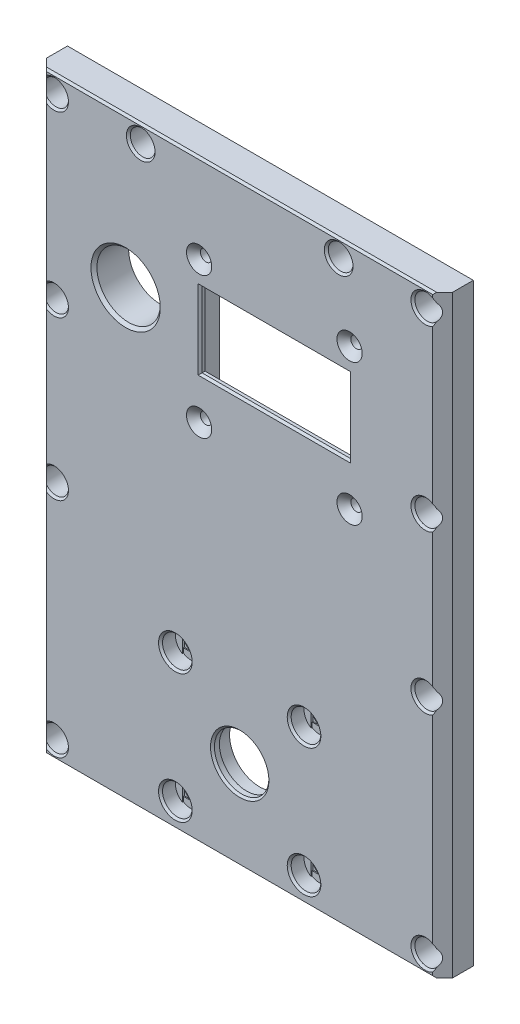
SolidWorks part; units mm, degrees
ref_plane "Front Plane" through (0, 0, 0) normal (0, 0, 1) x (1, 0, 0)
ref_plane "Top Plane" through (0, 0, 0) normal (0, 1, 0) x (1, 0, 0)
ref_plane "Right Plane" through (0, 0, 0) normal (1, 0, 0) x (0, 0, -1)
sketch "Sketch1" plane through (0, 0, 0) normal (0, 0, 1) x (1, 0, 0)
  line L1 (-41, -60) -> (41, -60)
  line L2 (-41, -60) -> (-41, 60)
  line L3 (-41, 60) -> (41, 60)
  line L4 (41, -60) -> (41, 60)
  line L5 (-41, -60) -> (41, 60) construction
  line L6 (-41, 60) -> (41, -60) construction
  line L7 (-34, -53) -> (34, -53)
  line L8 (-34, -53) -> (-34, 53)
  line L9 (-34, 53) -> (34, 53)
  line L10 (34, -53) -> (34, 53)
  line L11 (-34, -53) -> (34, 53) construction
  line L12 (-34, 53) -> (34, -53) construction
  point P0 (0, 0)
  point P6 (0, 0)
  dimension "D1" = 120
  dimension "D2" = 82
  dimension "D3" = 7
  dimension "D4" = 7
extrude "Boss-Extrude1" add sketch "Sketch1" along normal blind 7
sketch "Sketch2" plane through (0, 0, 7) normal (0, 0, 1) x (1, 0, 0)
  line L0 (34, -53) -> (34, 53) construction
  line L1 (-34, -53) -> (34, -53)
  line L2 (-34, -53) -> (-34, -17)
  line L3 (-34, -17) -> (34, -17)
  line L4 (34, -53) -> (34, -17)
  dimension "D1" = 36
extrude "Boss-Extrude2" add sketch "Sketch2" against normal up to surface (7 mm away) up to face at (0, 0, 0)
sketch "Sketch3" plane through (0, 0, 0) normal (0, 0, -1) x (-1, 0, 0)
  line L0 (0, -60) -> (0, -42) construction
  line L1 (41, -60) -> (-41, -60) construction
  circle A0 centre (0, -42) radius 5.5
  dimension "D1" = 11
  dimension "D2" = 18
extrude "Cut-Extrude1" cut sketch "Sketch3" against normal through all
sketch "Sketch4" plane through (0, 0, 0) normal (0, 0, -1) x (-1, 0, 0)
  circle A0 centre (0, -42) radius 6.05
  dimension "D1" = 12.1
extrude "Cut-Extrude2" cut sketch "Sketch4" against normal offset from surface (5.6 mm away) 1.4 up to face at (-5.5, -42, 7)
sketch "Sketch5" plane through (0, 0, 0) normal (0, 0, -1) x (-1, 0, 0)
  circle A0 centre (0, -42) radius 11.1
  dimension "D1" = 22.2
extrude "Cut-Extrude3" cut sketch "Sketch5" against normal offset from surface (3 mm away) 2.6 up to face at (-6.05, -42, 5.6)
sketch "Sketch6" plane through (0, 0, 0) normal (0, 0, -1) x (-1, 0, 0)
  line L1 (-13, -55) -> (13, -55) construction
  line L2 (-13, -55) -> (-13, -29) construction
  line L3 (-13, -29) -> (13, -29) construction
  line L4 (13, -55) -> (13, -29) construction
  line L5 (-13, -55) -> (13, -29) construction
  line L6 (-13, -29) -> (13, -55) construction
  circle A0 centre (-13, -29) radius 1.6
  circle A1 centre (13, -29) radius 1.6
  circle A2 centre (13, -55) radius 1.6
  circle A3 centre (-13, -55) radius 1.6
  point P0 (0, -42)
  dimension "D2" = 3.2
  dimension "D1" = 26
extrude "Cut-Extrude4" cut sketch "Sketch6" against normal through all
sketch "Sketch7" plane through (0, 0, 0) normal (0, 0, -1) x (-1, 0, 0)
  line L1 (-25, -61) -> (25, -61)
  line L2 (-25, -61) -> (-25, -23)
  line L3 (-25, -23) -> (25, -23)
  line L4 (25, -61) -> (25, -23)
  line L5 (-25, -61) -> (25, -23) construction
  line L6 (-25, -23) -> (25, -61) construction
  point P0 (0, -42)
  dimension "D1" = 50
  dimension "D2" = 38
extrude "Cut-Extrude5" cut sketch "Sketch7" against normal blind 1
sketch "Sketch8" plane through (0, 0, 7) normal (0, 0, 1) x (1, 0, 0)
  circle A0 centre (-13, -29) radius 3
  circle A1 centre (13, -29) radius 3
  circle A2 centre (13, -55) radius 3
  circle A3 centre (-13, -55) radius 3
  dimension "D1" = 6
extrude "Cut-Extrude6" cut sketch "Sketch8" against normal blind 3
sketch "Sketch9" plane through (0, 0, 7) normal (0, 0, 1) x (1, 0, 0)
  line L0 (-41, 60) -> (-41, -60) construction
  line L1 (-37.5, -56.5) -> (37.5, -56.5) construction
  line L2 (-37.5, -56.5) -> (-37.5, 56.5) construction
  line L3 (-37.5, 56.5) -> (37.5, 56.5) construction
  line L4 (37.5, -56.5) -> (37.5, 56.5) construction
  line L5 (-37.5, -56.5) -> (37.5, 56.5) construction
  line L6 (-37.5, 56.5) -> (37.5, -56.5) construction
  line L7 (41, 60) -> (-41, 60) construction
  circle A0 centre (-37.5, 56.5) radius 1.5
  circle A1 centre (37.5, 56.5) radius 1.5
  circle A2 centre (37.5, -56.5) radius 1.5
  circle A3 centre (-37.5, -56.5) radius 1.5
  circle A6 centre (-37.5, 20.5) radius 1.5
  circle A7 centre (-37.5, -11.5) radius 1.5
  circle A8 centre (37.5, -11.5) radius 1.5
  circle A9 centre (37.5, 20.5) radius 1.5
  point P0 (0, 0)
  dimension "D3" = 3
  dimension "D4" = 45
  dimension "D5" = 36
  dimension "D1" = 3.5
  dimension "D2" = 3.5
extrude "Cut-Extrude7" cut sketch "Sketch9" against normal through all
sketch "Sketch10" plane through (0, 0, 7) normal (0, 0, 1) x (1, 0, 0)
  circle A0 centre (-37.5, 56.5) radius 2.5
  circle A1 centre (37.5, 56.5) radius 2.5
  circle A2 centre (-37.5, 20.5) radius 2.5
  circle A3 centre (-37.5, -11.5) radius 2.5
  circle A4 centre (-37.5, -56.5) radius 2.5
  circle A5 centre (37.5, -56.5) radius 2.5
  circle A6 centre (37.5, 20.5) radius 2.5
  circle A7 centre (37.5, -11.5) radius 2.5
  dimension "D1" = 5
extrude "Cut-Extrude8" cut sketch "Sketch10" against normal blind 5
chamfer "Chamfer1" distance 2 angle 45 2 edges at (-41, 0, 7) (41, 0, 7)
sketch "Sketch11" plane through (0, 0, 7) normal (0, 0, 1) x (1, 0, 0)
  line L0 (34, -17) -> (34, 53) construction
  line L1 (-34, -17) -> (34, -17)
  line L2 (-34, -17) -> (-34, 2)
  line L3 (-34, 2) -> (34, 2)
  line L4 (34, -17) -> (34, 2)
  line L5 (-39, -60) -> (39, -60) construction
  dimension "D1" = 62
extrude "Boss-Extrude3" add sketch "Sketch11" against normal up to surface (7 mm away) up to face at (39, 56.5, 0)
sketch "Sketch12" plane through (0, 0, 2) normal (0, 0, 1) x (1, 0, 0)
  line L2 (-39, -58.5) -> (-39, -54.5)
  line L4 (-36, -58.5) -> (-36, -54.5)
  line L5 (-39, -58.5) -> (-36, -54.5) construction
  line L6 (-39, -54.5) -> (-36, -58.5) construction
  line L8 (-39, -13.5) -> (-39, -9.5)
  line L10 (-36, -13.5) -> (-36, -9.5)
  line L11 (-39, -13.5) -> (-36, -9.5) construction
  line L12 (-39, -9.5) -> (-36, -13.5) construction
  line L14 (-39, 18.5) -> (-39, 22.5)
  line L16 (-36, 18.5) -> (-36, 22.5)
  line L17 (-39, 18.5) -> (-36, 22.5) construction
  line L18 (-39, 22.5) -> (-36, 18.5) construction
  line L20 (-39, 54.5) -> (-39, 58.5)
  line L22 (-36, 54.5) -> (-36, 58.5)
  line L23 (-39, 54.5) -> (-36, 58.5) construction
  line L24 (-39, 58.5) -> (-36, 54.5) construction
  arc A0 (-39, -58.5) -> (-39, -54.5) centre (-37.5, -56.5) ccw construction
  circle A1 centre (-37.5, -11.5) radius 2.5 construction
  circle A2 centre (-37.5, 20.5) radius 2.5 construction
  arc A3 (-39, 54.5) -> (-39, 58.5) centre (-37.5, 56.5) ccw construction
  circle A4 centre (-37.5, 56.5) radius 1.5 construction
  circle A5 centre (-37.5, 56.5) radius 2.5 construction
  arc A6 (-36, 58.5) -> (-39, 58.5) centre (-37.5, 56.5) ccw
  arc A7 (-39, 54.5) -> (-36, 54.5) centre (-37.5, 56.5) ccw
  circle A8 centre (-37.5, 20.5) radius 1.5 construction
  arc A9 (-39, 18.5) -> (-36, 18.5) centre (-37.5, 20.5) ccw
  arc A10 (-36, 22.5) -> (-39, 22.5) centre (-37.5, 20.5) ccw
  circle A11 centre (-37.5, -11.5) radius 1.5 construction
  arc A12 (-39, -13.5) -> (-36, -13.5) centre (-37.5, -11.5) ccw
  arc A13 (-36, -9.5) -> (-39, -9.5) centre (-37.5, -11.5) ccw
  circle A14 centre (-37.5, -56.5) radius 1.5 construction
  arc A16 (-39, -58.5) -> (-36, -58.5) centre (-37.5, -56.5) ccw
  arc A18 (-36, -54.5) -> (-39, -54.5) centre (-37.5, -56.5) ccw
  point P0 (-37.5, -56.5)
  point P9 (-37.5, -11.5)
  point P17 (-37.5, 20.5)
  point P25 (-37.5, 56.5)
extrude "Cut-Extrude9" cut sketch "Sketch12" against normal blind 0.2
sketch "Sketch13" plane through (0, 0, 1.8) normal (0, 0, 1) x (1, 0, 0)
  line L0 (-36, -56.5) -> (-36, -54.5) construction
  line L1 (-39, -58) -> (-36, -58)
  line L2 (-39, -58) -> (-39, -55)
  line L3 (-39, -55) -> (-36, -55)
  line L4 (-36, -58) -> (-36, -55)
  line L5 (-39, -58) -> (-36, -55) construction
  line L6 (-39, -55) -> (-36, -58) construction
  line L7 (-36, -11.5) -> (-36, -9.5) construction
  line L8 (-39, -13) -> (-36, -13)
  line L9 (-39, -13) -> (-39, -10)
  line L10 (-39, -10) -> (-36, -10)
  line L11 (-36, -13) -> (-36, -10)
  line L12 (-39, -13) -> (-36, -10) construction
  line L13 (-39, -10) -> (-36, -13) construction
  line L14 (-36, 18.5) -> (-36, 22.5) construction
  line L15 (-39, 19) -> (-36, 19)
  line L16 (-39, 19) -> (-39, 22)
  line L17 (-39, 22) -> (-36, 22)
  line L18 (-36, 19) -> (-36, 22)
  line L19 (-39, 19) -> (-36, 22) construction
  line L20 (-39, 22) -> (-36, 19) construction
  line L21 (-36, 54.5) -> (-36, 58.5) construction
  line L22 (-39, 55) -> (-36, 55)
  line L23 (-39, 55) -> (-39, 58)
  line L24 (-39, 58) -> (-36, 58)
  line L25 (-36, 55) -> (-36, 58)
  line L26 (-39, 55) -> (-36, 58) construction
  line L27 (-39, 58) -> (-36, 55) construction
  arc A0 (-36, -56.5) -> (-39, -56.5) centre (-37.5, -56.5) ccw construction
  arc A1 (-36, -11.5) -> (-39, -11.5) centre (-37.5, -11.5) ccw construction
  arc A2 (-36, 20.5) -> (-39, 20.5) centre (-37.5, 20.5) ccw construction
  arc A3 (-36, 56.5) -> (-39, 56.5) centre (-37.5, 56.5) ccw construction
  point P0 (-37.5, -56.5)
  point P11 (-37.5, -11.5)
  point P22 (-37.5, 20.5)
  point P33 (-37.5, 56.5)
extrude "Cut-Extrude10" cut sketch "Sketch13" against normal blind 0.2
sketch "Sketch14" plane through (0, 0, 4) normal (0, 0, 1) x (1, 0, 0)
  line L2 (-14.6, -31.5377) -> (-14.6, -26.4623)
  line L4 (-11.4, -31.5377) -> (-11.4, -26.4623)
  line L5 (-14.6, -31.5377) -> (-11.4, -26.4623) construction
  line L6 (-14.6, -26.4623) -> (-11.4, -31.5377) construction
  line L8 (-14.6, -57.5377) -> (-14.6, -52.4623)
  line L10 (-11.4, -57.5377) -> (-11.4, -52.4623)
  line L11 (-14.6, -57.5377) -> (-11.4, -52.4623) construction
  line L12 (-14.6, -52.4623) -> (-11.4, -57.5377) construction
  circle A0 centre (-13, -29) radius 3 construction
  circle A1 centre (-13, -55) radius 3 construction
  circle A2 centre (-13, -29) radius 3 construction
  arc A3 (-14.6, -31.5377) -> (-11.4, -31.5377) centre (-13, -29) ccw
  arc A4 (-14.6, -57.5377) -> (-11.4, -57.5377) centre (-13, -55) ccw
  circle A5 centre (-13, -29) radius 1.6 construction
  circle A6 centre (-13, -55) radius 1.6 construction
  arc A7 (-11.4, -26.4623) -> (-14.6, -26.4623) centre (-13, -29) ccw
  arc A8 (-11.4, -52.4623) -> (-14.6, -52.4623) centre (-13, -55) ccw
  point P0 (-13, -29)
  point P8 (-13, -55)
extrude "Cut-Extrude11" cut sketch "Sketch14" against normal blind 0.2
sketch "Sketch15" plane through (0, 0, 3.8) normal (0, 0, 1) x (1, 0, 0)
  line L0 (-11.4, -29) -> (-11.4, -26.4623) construction
  line L1 (-14.6, -30.6) -> (-11.4, -30.6)
  line L2 (-14.6, -30.6) -> (-14.6, -27.4)
  line L3 (-14.6, -27.4) -> (-11.4, -27.4)
  line L4 (-11.4, -30.6) -> (-11.4, -27.4)
  line L5 (-14.6, -30.6) -> (-11.4, -27.4) construction
  line L6 (-14.6, -27.4) -> (-11.4, -30.6) construction
  line L7 (-11.4, -55) -> (-11.4, -52.4623) construction
  line L8 (-14.6, -56.6) -> (-11.4, -56.6)
  line L9 (-14.6, -56.6) -> (-14.6, -53.4)
  line L10 (-14.6, -53.4) -> (-11.4, -53.4)
  line L11 (-11.4, -56.6) -> (-11.4, -53.4)
  line L12 (-14.6, -56.6) -> (-11.4, -53.4) construction
  line L13 (-14.6, -53.4) -> (-11.4, -56.6) construction
  arc A0 (-11.4, -55) -> (-14.6, -55) centre (-13, -55) ccw construction
  arc A1 (-14.6, -29) -> (-11.4, -29) centre (-13, -29) ccw construction
  point P0 (-13, -29)
  point P8 (-13, -55)
extrude "Cut-Extrude12" cut sketch "Sketch15" against normal blind 0.2
mirror "Mirror1" about plane through (0, 0, 0) normal (1, 0, 0) of "Cut-Extrude10", "Cut-Extrude11", "Cut-Extrude12", "Cut-Extrude9"
chamfer "Chamfer2" distance 0.4 angle 45 4 edges at (34, 27.5, 7) (0, 53, 7) (0, 2, 7) (-34, 27.5, 7)
chamfer "Chamfer3" distance 0.8 angle 45 2 edges at (-41, 0, 0) (41, 0, 0)
sketch "Sketch16" plane through (0, 0, 0) normal (1, 0, 0) x (0, 0, -1)
  line L0 (0, -4) -> (0, -15.4)
  line L1 (0, 60) -> (0, -60) construction
  line L2 (0, -15.4) -> (3.2, -12.2)
  line L3 (3.2, -12.2) -> (3.2, -7.2)
  line L4 (3.2, -7.2) -> (0, -4)
  line L5 (0, -15.4) -> (0, -19.4) construction
  line L6 (0.6, -7.7) -> (2.6, -7.7)
  line L7 (0.6, -7.7) -> (0.6, -11.7)
  line L8 (0.6, -11.7) -> (2.6, -11.7)
  line L9 (2.6, -7.7) -> (2.6, -11.7)
  line L10 (-1.046, -17.4) -> (12.8392, -17.4) construction
  line L11 (2.6, -27.1) -> (2.6, -23.1)
  line L12 (0.6, -23.1) -> (2.6, -23.1)
  line L13 (0.6, -27.1) -> (0.6, -23.1)
  line L14 (0.6, -27.1) -> (2.6, -27.1)
  line L15 (3.2, -27.6) -> (0, -30.8)
  line L16 (3.2, -22.6) -> (3.2, -27.6)
  line L17 (0, -19.4) -> (3.2, -22.6)
  line L18 (0, -30.8) -> (0, -19.4)
  point P10 (2.6, -9.7)
  point P11 (3.2, -9.7)
  point P24 (0, -17.4)
  dimension "D1" = 5
  dimension "D2" = 2
  dimension "D3" = 0.6
  dimension "D4" = 0.6
  dimension "D5" = 45
  dimension "D6" = 4
  dimension "D7" = 4
  dimension "D8" = 4
extrude "Boss-Extrude4" add sketch "Sketch16" along normal mid plane 2
pattern_linear "LPattern1" count 2 spacing 20 along (1, 0, 0) count 2 spacing 20 along (-1, 0, 0) of "Boss-Extrude4"
sketch "Sketch17" plane through (0, 0, 0) normal (0, 0, -1) x (-1, 0, 0)
  line L0 (-20, 56.5) -> (20, 56.5) construction
  line L1 (-40.2, 60) -> (40.2, 60) construction
  circle A0 centre (-37.5, 56.5) radius 1.5 construction
  circle A1 centre (-37.5, 56.5) radius 1.5 construction
  circle A2 centre (-20, 56.5) radius 1.5
  circle A3 centre (20, 56.5) radius 1.5
  point P3 (0, 56.5)
  point P6 (0, 60)
  dimension "D1" = 40
extrude "Cut-Extrude13" cut sketch "Sketch17" against normal through all
sketch "Sketch18" plane through (0, 0, 7) normal (0, 0, 1) x (1, 0, 0)
  circle A0 centre (-20, 56.5) radius 2.5
  circle A1 centre (20, 56.5) radius 2.5
  arc A2 (-39, 54.5) -> (-39, 58.5) centre (-37.5, 56.5) ccw construction
extrude "Cut-Extrude14" cut sketch "Sketch18" against normal up to surface (5 mm away) up to face at (35.5, 56.5, 2)
sketch "Sketch19" plane through (0, 0, 2) normal (0, 0, 1) x (1, 0, 0)
  line L2 (-21.5, 54.5) -> (-21.5, 58.5)
  line L4 (-18.5, 54.5) -> (-18.5, 58.5)
  line L5 (-21.5, 54.5) -> (-18.5, 58.5) construction
  line L6 (-21.5, 58.5) -> (-18.5, 54.5) construction
  line L8 (18.5, 54.5) -> (18.5, 58.5)
  line L10 (21.5, 54.5) -> (21.5, 58.5)
  line L11 (18.5, 54.5) -> (21.5, 58.5) construction
  line L12 (18.5, 58.5) -> (21.5, 54.5) construction
  circle A0 centre (-20, 56.5) radius 2.5 construction
  circle A1 centre (20, 56.5) radius 2.5 construction
  circle A2 centre (20, 56.5) radius 1.5 construction
  circle A3 centre (-20, 56.5) radius 1.5 construction
  circle A4 centre (-20, 56.5) radius 2.5 construction
  arc A5 (18.5, 54.5) -> (21.5, 54.5) centre (20, 56.5) ccw
  arc A6 (-18.5, 58.5) -> (-21.5, 58.5) centre (-20, 56.5) ccw
  arc A7 (21.5, 58.5) -> (18.5, 58.5) centre (20, 56.5) ccw
  arc A8 (-21.5, 54.5) -> (-18.5, 54.5) centre (-20, 56.5) ccw
  point P0 (-20, 56.5)
  point P8 (20, 56.5)
extrude "Cut-Extrude15" cut sketch "Sketch19" against normal blind 0.2
sketch "Sketch20" plane through (0, 0, 1.8) normal (0, 0, 1) x (1, 0, 0)
  line L0 (-18.5, 54.5) -> (-18.5, 58.5) construction
  line L1 (-21.5, 55) -> (-18.5, 55)
  line L2 (-21.5, 55) -> (-21.5, 58)
  line L3 (-21.5, 58) -> (-18.5, 58)
  line L4 (-18.5, 55) -> (-18.5, 58)
  line L5 (-21.5, 55) -> (-18.5, 58) construction
  line L6 (-21.5, 58) -> (-18.5, 55) construction
  line L7 (21.5, 56.5) -> (21.5, 58.5) construction
  line L8 (18.5, 55) -> (21.5, 55)
  line L9 (18.5, 55) -> (18.5, 58)
  line L10 (18.5, 58) -> (21.5, 58)
  line L11 (21.5, 55) -> (21.5, 58)
  line L12 (18.5, 55) -> (21.5, 58) construction
  line L13 (18.5, 58) -> (21.5, 55) construction
  arc A0 (18.5, 56.5) -> (21.5, 56.5) centre (20, 56.5) ccw construction
  point P0 (-20, 56.5)
  point P8 (20, 56.5)
extrude "Cut-Extrude16" cut sketch "Sketch20" against normal blind 0.2
sketch "Skizze4" plane through (0, 0, 0) normal (0, 0, -1) x (-1, 0, 0)
  line L1 (21, -4) -> (-21, -4)
  line L2 (21, -4) -> (21, -30.8)
  line L3 (21, -30.8) -> (-21, -30.8)
  line L4 (-21, -4) -> (-21, -30.8)
extrude "Schnitt-Linear austragen1" cut sketch "Skizze4" along normal up to surface (3.2 mm away) up to face at (-20, -9.7, -3.2)
sketch "Skizze6" plane through (0, 0, 7) normal (0, 0, 1) x (1, 0, 0)
  line L0 (12.4, 53.4) -> (34.4, 31.4) construction
  line L1 (34.4, 53.4) -> (12.4, 53.4)
  line L2 (34.4, 53.4) -> (34.4, 31.4)
  line L3 (34.4, 31.4) -> (12.4, 31.4)
  line L4 (12.4, 53.4) -> (12.4, 31.4)
  line L5 (23.4, 53.4) -> (23.4, 31.4) construction
  circle A0 centre (23.4, 41.4) radius 8.25
  point P10 (23.4, 42.4)
  dimension "D1" = 16.5
  dimension "D2" = 22
  dimension "D3" = 22
  dimension "D4" = 1
extrude "Aufsatz-Linear austragen1" add sketch "Skizze6" against normal up to surface (7 mm away) up to face at (0, -20.75, 0)
sketch "Skizze7" plane through (0, 0, 7) normal (0, 0, 1) x (1, 0, 0)
  circle A0 centre (23.4, 41.4) radius 9.25
  dimension "D1" = 18.5
extrude "Schnitt-Linear austragen2" cut sketch "Skizze7" against normal blind 1.6
chamfer "Fase6" distance 0.5 angle 45 2 edges at (12.4, 42.4, 7) (23.4, 31.4, 7)
chamfer "Fase7" distance 4 angle 45 1 edges at (12.4, 31.4, 3.25)
chamfer "Fase8" distance 1 angle 45 1 edges at (31.65, 41.4, 5.4)
mirror "Mirror2" about plane through (0, 0, 0) normal (1, 0, 0) of "Fase6", "Schnitt-Linear austragen2", "Fase8", "Aufsatz-Linear austragen1", "Fase7"
sketch "Sketch21" plane through (0, 0, 7) normal (0, 0, 1) x (1, 0, 0)
  line L0 (34.4, 31.9) -> (34.4, 1.6) construction
  line L1 (-34.4, 31.9) -> (-15.9, 31.9)
  line L2 (-34.4, 31.9) -> (-34.4, 15.9)
  line L3 (-34.4, 15.9) -> (34.4, 15.9)
  line L4 (34.4, 31.9) -> (34.4, 15.9)
  line L5 (-15.9, 31.9) -> (-12.4, 35.4)
  line L6 (-12.4, 35.4) -> (-12.4, 31.9)
  line L7 (12.4, 35.4) -> (15.9, 31.9)
  line L8 (12.4, 35.4) -> (12.4, 31.9)
  line L9 (-12.4, 31.9) -> (12.4, 31.9)
  line L10 (15.9, 31.9) -> (34.4, 31.9)
  dimension "D1" = 16
extrude "Boss-Extrude5" add sketch "Sketch21" against normal up to surface (7 mm away) up to face at (0, 30.64, 0)
chamfer "Chamfer4" distance 0.5 angle 45 7 edges at (12.65, 35.15, 7) (12.4, 33.65, 7) (0, 31.9, 7) (-12.4, 33.65, 7) (-12.65, 35.15, 7) (12.4, 35.4, 6.75) (-12.4, 35.4, 6.75)
sketch "Sketch22" plane through (0, 0, 0) normal (0, 0, -1) x (-1, 0, 0)
  line L0 (0, 31.9) -> (0, 15.9) construction
  line L1 (-12.4, 31.9) -> (12.4, 31.9) construction
  line L2 (34, 15.9) -> (-34, 15.9) construction
  line L4 (-18.95, 17.75) -> (18.95, 17.75)
  line L5 (-18.95, 17.75) -> (-18.95, 30.05)
  line L6 (-18.95, 30.05) -> (18.95, 30.05)
  line L7 (18.95, 17.75) -> (18.95, 30.05)
  line L8 (-18.95, 17.75) -> (18.95, 30.05) construction
  line L9 (-18.95, 30.05) -> (18.95, 17.75) construction
  point P6 (0, 23.9)
  dimension "D1" = 37.9
  dimension "D2" = 12.3
extrude "Cut-Extrude17" cut sketch "Sketch22" against normal offset from surface (6.4 mm away) 0.6 up to face at (0, 8.75, 7)
sketch "Sketch23" plane through (0, 0, 6.4) normal (0, 0, -1) x (-1, 0, 0)
  line L0 (-18.95, 30.05) -> (-18.95, 17.75) construction
  line L1 (-12.95, 18.55) -> (12.05, 18.55)
  line L2 (-12.95, 18.55) -> (-12.95, 28.55)
  line L3 (-12.95, 28.55) -> (12.05, 28.55)
  line L4 (12.05, 18.55) -> (12.05, 28.55)
  line L5 (-12.95, 18.55) -> (12.05, 28.55) construction
  line L6 (-12.95, 28.55) -> (12.05, 18.55) construction
  line L7 (-18.95, 30.05) -> (18.95, 30.05) construction
  point P0 (-0.45, 23.55)
  dimension "D1" = 25
  dimension "D2" = 10
  dimension "D3" = 6
  dimension "D4" = 1.5
extrude "Cut-Extrude18" cut sketch "Sketch23" against normal through all
chamfer "Chamfer5" distance 0.4 angle 45 1 edges at (0, 15.9, 7)
sketch "Sketch24" plane through (0, 0, 7) normal (0, 0, 1) x (1, 0, 0)
  line L1 (-12.9, 53.4) -> (12.9, 53.4)
  line L2 (-12.9, 53.4) -> (-12.9, 31.4)
  line L3 (-12.9, 31.4) -> (12.9, 31.4)
  line L4 (12.9, 53.4) -> (12.9, 31.4)
  line L5 (-12.4, 53) -> (12.4, 53)
  line L6 (-12.4, 53) -> (-12.4, 31.9)
  line L7 (-12.4, 31.9) -> (12.4, 31.9)
  line L8 (12.4, 53) -> (12.4, 31.9)
extrude "Boss-Extrude6" add sketch "Sketch24" against normal up to vertex (0.5 mm away) up to point (12.4, 31.9, 6.5)
chamfer "Chamfer7" distance 3 angle 45 4 edges at (12.4, 31.9, 3.5) (12.4, 53, 3.5) (-12.4, 53, 3.5) (-12.4, 31.9, 3.5)
chamfer "Chamfer8" distance 0.5 angle 45 8 edges at (12.4, 42.45, 7) (0, 31.9, 7) (0, 53, 7) (-12.4, 42.45, 7) (10.9, 33.4, 7) (10.9, 51.5, 7) (-10.9, 51.5, 7) (-10.9, 33.4, 7)
chamfer "Chamfer9" distance 0.8 angle 45 6 edges at (-34, 8.95, 0) (0, 15.9, 0) (34, 8.95, 0) (0, 2, 0) (-32.6, -60, 0) (0, 60, 0)
sketch "Sketch28" plane through (0, 0, 7) normal (0, 0, 1) x (1, 0, 0)
  circle A0 centre (23.4, 41.4) radius 10
  dimension "D1" = 20
extrude "Boss-Extrude8" add sketch "Sketch28" against normal up to surface (7 mm away) up to face at (0, 8.95, 0)
sketch "Sketch29" plane through (0, 0, 0) normal (0, 0, -1) x (-1, 0, 0)
  line L0 (-9.4, 53) -> (9.4, 53) construction
  line L1 (34.8, 53) -> (-34.8, 53)
  line L2 (34.8, 53) -> (34.8, 1.2)
  line L3 (34.8, 1.2) -> (-34.8, 1.2)
  line L4 (-34.8, 53) -> (-34.8, 1.2)
  line L5 (34.8, 1.2) -> (-34.8, 1.2) construction
  line L6 (34.8, 16.7) -> (34.8, 1.2) construction
  line L7 (-34.8, 1.2) -> (-34.8, 16.7) construction
extrude "Boss-Extrude9" add sketch "Sketch29" against normal up to surface (7 mm away) up to face at (0, 42.45, 7)
sketch "Sketch30" plane through (0, 0, 7) normal (0, 0, 1) x (1, 0, 0)
  line L0 (9.4, 53) -> (10.1071, 53) construction
  line L1 (10.1071, 53) -> (9.6071, 53.5) construction
  line L2 (-10.1071, 53) -> (-9.4, 53) construction
  line L3 (-9.6071, 53.5) -> (-10.1071, 53) construction
  line L4 (9.6071, 53.5) -> (-9.6071, 53.5) construction
  line L5 (-9.4, 53) -> (9.4, 53) construction
  line L6 (9.4, 53) -> (10.1071, 53)
  line L7 (10.1071, 53) -> (9.6071, 53.5)
  line L8 (-10.1071, 53) -> (-9.4, 53)
  line L9 (-9.6071, 53.5) -> (-10.1071, 53)
  line L10 (9.6071, 53.5) -> (-9.6071, 53.5)
  line L11 (-9.4, 53) -> (9.4, 53)
extrude "Boss-Extrude10" add sketch "Sketch30" against normal up to surface (7 mm away) up to face at (0, -20.75, 0)
sketch "Sketch31" plane through (0, 0, 0) normal (0, 0, -1) x (-1, 0, 0)
  line L0 (-7, 55.2531) -> (-7, 0.5469) construction
  line L1 (-24.8, 11.05) -> (10.8, 11.05) construction
  line L2 (-24.8, 11.05) -> (-24.8, 44.75) construction
  line L3 (-24.8, 44.75) -> (10.8, 44.75) construction
  line L4 (10.8, 11.05) -> (10.8, 44.75) construction
  line L5 (-24.8, 11.05) -> (10.8, 44.75) construction
  line L6 (-24.8, 44.75) -> (10.8, 11.05) construction
  line L7 (-22.2, 13.65) -> (8.2, 13.65) construction
  line L8 (-22.2, 13.65) -> (-22.2, 42.15) construction
  line L9 (-22.2, 42.15) -> (8.2, 42.15) construction
  line L10 (8.2, 13.65) -> (8.2, 42.15) construction
  line L11 (-22.2, 13.65) -> (8.2, 42.15) construction
  line L12 (-22.2, 42.15) -> (8.2, 13.65) construction
  line L13 (-25.05, 10.8) -> (11.05, 10.8)
  line L14 (-25.05, 10.8) -> (-25.05, 45)
  line L15 (-25.05, 45) -> (11.05, 45)
  line L16 (11.05, 10.8) -> (11.05, 45)
  line L17 (-25.05, 10.8) -> (11.05, 45) construction
  line L18 (-25.05, 45) -> (11.05, 10.8) construction
  line L19 (-22, 22.2) -> (8, 22.2) construction
  line L20 (-22, 22.2) -> (-22, 37.4) construction
  line L21 (-22, 37.4) -> (8, 37.4) construction
  line L22 (8, 22.2) -> (8, 37.4) construction
  line L23 (-22, 22.2) -> (8, 37.4) construction
  line L24 (-22, 37.4) -> (8, 22.2) construction
  line L25 (-7, 29.8) -> (23, 29.8) construction
  line L26 (23, 17.8) -> (23, 41.8) construction
  line L27 (-41, -60) -> (-41, 60) construction
  line L28 (-41, 60) -> (41, 60) construction
  circle A0 centre (-22.2, 42.15) radius 1.5 construction
  circle A1 centre (8.2, 42.15) radius 1.5 construction
  circle A2 centre (8.2, 13.65) radius 1.5 construction
  circle A3 centre (-22.2, 13.65) radius 1.5 construction
  circle A4 centre (23, 41.8) radius 6.3
  circle A5 centre (23, 17.8) radius 6.3
  circle A6 centre (23, 17.8) radius 7
  circle A7 centre (23, 41.8) radius 7
  point P2 (-7, 27.9)
  point P7 (-7, 27.9)
  point P16 (-7, 27.9)
  point P21 (-7, 29.8)
  point P32 (23, 29.8)
  point P40 (0, 60)
  dimension "D5" = 3
  dimension "D12" = 15
  dimension "D13" = 12.6
  dimension "D14" = 14
  dimension "D1" = 35.6
  dimension "D2" = 33.7
  dimension "D3" = 30.4
  dimension "D4" = 28.5
  dimension "D6" = 0.25
  dimension "D7" = 0.25
  dimension "D8" = 15.2
  dimension "D9" = 30
  dimension "D10" = 7.35
  dimension "D11" = 34
  dimension "D15" = 24
  dimension "D16" = 30
sketch "Sketch32" plane through (0, 0, 0) normal (0, 0, -1) x (-1, 0, 0)
  line L0 (-25.05, 10.8) -> (-25.05, 45) construction
  line L1 (-25.05, 10.8) -> (11.05, 10.8) construction
  line L2 (11.05, 10.8) -> (11.05, 45) construction
  line L3 (-25.05, 45) -> (11.05, 45) construction
  line L4 (-25.05, 10.8) -> (-25.05, 45)
  line L5 (-25.05, 10.8) -> (11.05, 10.8)
  line L6 (11.05, 10.8) -> (11.05, 45)
  line L7 (-25.05, 45) -> (11.05, 45)
extrude "Cut-Extrude19" cut sketch "Sketch32" against normal offset from surface (6 mm away) 1 up to face at (-17.5, 56.5, 7)
sketch "Sketch33" plane through (0, 0, 6) normal (0, 0, -1) x (-1, 0, 0)
  line L0 (-22, 22.2) -> (-22, 37.4) construction
  line L1 (-22, 22.2) -> (8, 22.2) construction
  line L2 (8, 22.2) -> (8, 37.4) construction
  line L3 (-22, 37.4) -> (8, 37.4) construction
  line L4 (-22, 22.2) -> (-22, 37.4)
  line L5 (-22, 22.2) -> (8, 22.2)
  line L6 (8, 22.2) -> (8, 37.4)
  line L7 (-22, 37.4) -> (8, 37.4)
extrude "Cut-Extrude20" cut sketch "Sketch33" against normal through all
sketch "Sketch35" plane through (0, 0, 6) normal (0, 0, -1) x (-1, 0, 0)
  line L1 (-25.05, 10.8) -> (-20.2, 10.8)
  line L2 (-25.05, 10.8) -> (-25.05, 15.65)
  line L3 (-25.05, 15.65) -> (-20.2, 15.65)
  line L4 (-20.2, 10.8) -> (-20.2, 15.65)
  line L5 (11.05, 10.8) -> (6.2, 10.8)
  line L6 (11.05, 10.8) -> (11.05, 15.65)
  line L7 (11.05, 15.65) -> (6.2, 15.65)
  line L8 (6.2, 10.8) -> (6.2, 15.65)
  line L9 (-25.05, 45) -> (-20.2, 45)
  line L10 (-25.05, 45) -> (-25.05, 40.15)
  line L11 (-25.05, 40.15) -> (-20.2, 40.15)
  line L12 (-20.2, 45) -> (-20.2, 40.15)
  line L13 (11.05, 45) -> (6.2, 45)
  line L14 (11.05, 45) -> (11.05, 40.15)
  line L15 (11.05, 40.15) -> (6.2, 40.15)
  line L16 (6.2, 45) -> (6.2, 40.15)
  dimension "D1" = 2
  dimension "D2" = 2
  dimension "D3" = 2
  dimension "D4" = 2
extrude "Boss-Extrude11" add sketch "Sketch35" along normal blind 1.8
sketch "Sketch36" plane through (0, 0, 4.2) normal (0, 0, -1) x (-1, 0, 0)
  circle A0 centre (-22.2, 13.65) radius 1.15
  circle A1 centre (8.2, 13.65) radius 1.15
  circle A2 centre (8.2, 42.15) radius 1.15
  circle A3 centre (-22.2, 42.15) radius 1.15
  dimension "D1" = 2.3
extrude "Cut-Extrude22" cut sketch "Sketch36" against normal through all
chamfer "Chamfer10" distance 1.4 angle 45 4 edges at (-9.35, 13.65, 7) (21.05, 13.65, 7) (21.05, 42.15, 7) (-9.35, 42.15, 7)
sketch "Sketch37" plane through (0, 0, 0) normal (0, 0, -1) x (-1, 0, 0)
  line L0 (8, 22.2) -> (8, 37.4) construction
  line L1 (11.05, 10.8) -> (11.05, 45) construction
  circle A0 centre (23.05, 29.8) radius 6.4
  point P5 (8, 29.8)
  dimension "D1" = 12.8
  dimension "D2" = 12
extrude "Cut-Extrude23" cut sketch "Sketch37" against normal through all
chamfer "Chamfer11" distance 0.6 angle 45 1 edges at (-29.45, 29.8, 7)
chamfer "Chamfer12" distance 0.4 angle 45 4 edges at (7, 22.2, 7) (22, 29.8, 7) (-8, 29.8, 7) (7, 37.4, 7)
chamfer "Chamfer13" distance 0.4 angle 45 2 edges at (0, -60, 7) (0, 60, 7)
chamfer "Chamfer14" distance 0.4 angle 45 15 edges at (-5.5, -42, 7) (35, -56.5, 7) (35, -11.5, 7) (35, 20.5, 7) (35, 56.5, 7) (22.5, 56.5, 7) (-17.5, 56.5, 7) (-35, 56.5, 7) (-35, 20.5, 7) (-35, -11.5, 7) (-35, -56.5, 7) (-10, -55, 7) (16, -55, 7) (16, -29, 7) (-10, -29, 7)
